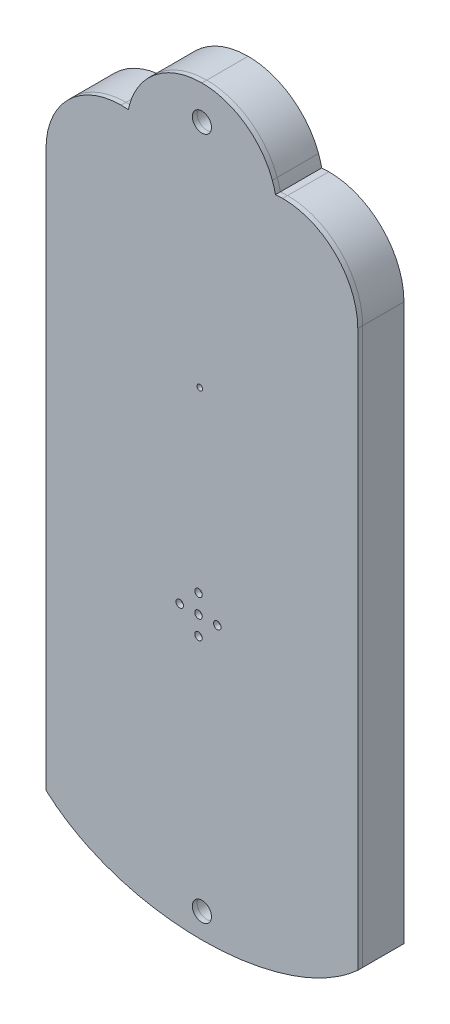
SolidWorks part; units mm, degrees
note: The reader was unsure of these and kept them because the rebuilt part matched: shared geometry of "草图3<3>", "草图3<4>", "草图3<5>", "草图3<6>", "草图3<7>", "草图5<4>", "草图5<5>", "草图5<6>".
ref_plane "前视基准面" through (0, 0, 0) normal (0, 0, 1) x (1, 0, 0)
ref_plane "上视基准面" through (0, 0, 0) normal (0, 1, 0) x (1, 0, 0)
ref_plane "右视基准面" through (0, 0, 0) normal (1, 0, 0) x (0, 0, -1)
other "Configuration Table"
sketch "草图1" plane through (0, 0, 0) normal (0, 0, 1) x (1, 0, 0)
  line L4 (-41.5008, 68.1408) -> (-41.5008, -79.8592)
  line L5 (41.5008, 68.1408) -> (41.5008, -79.8592)
  circle A0 centre (0, 95) radius 2.55
  circle A1 centre (0, -87) radius 2.55
  spline S0 degree 3 poles (41.5008, 68.1408) (41.5008, 79.1863) (32.5473, 88.1398) (21.5018, 88.1398) knots 0 0 0 0 1 1 1 1
  spline S1 degree 3 poles (21.5018, 88.1398) (20.8598, 88.1398) (20.2212, 88.108) (19.5933, 88.048) knots 1 1 1 1 2 2 2 2
  spline S2 degree 3 poles (19.5933, 88.048) (19.3887, 89.0464) (19.1064, 90.0201) (18.7607, 90.962) knots 2 2 2 2 3 3 3 3
  spline S3 degree 3 poles (18.7607, 90.962) (15.9385, 98.582) (8.6043, 104.0148) (0, 104.0148) knots 3 3 3 3 4 4 4 4
  spline S4 degree 3 poles (0, 104.0148) (-8.6043, 104.0148) (-15.9385, 98.582) (-18.7607, 90.962) knots 4 4 4 4 5 5 5 5
  spline S5 degree 3 poles (-18.7607, 90.962) (-19.1065, 90.0201) (-19.3887, 89.0464) (-19.5933, 88.048) knots 5 5 5 5 6 6 6 6
  spline S6 degree 3 poles (-19.5933, 88.048) (-20.2212, 88.108) (-20.8562, 88.1398) (-21.4983, 88.1398) knots 6 6 6 6 7 7 7 7
  spline S7 degree 3 poles (-21.4983, 88.1398) (-32.5473, 88.1398) (-41.5008, 79.1863) (-41.5008, 68.1408) knots 7 7 7 7 8 8 8 8
  spline S9 degree 3 poles (-41.5008, -79.8592) (-38.3893, -82.7026) (-34.5687, -85.2073) (-30.1978, -87.2781) knots 11 11 11 11 12 12 12 12
  spline S10 degree 3 poles (-30.1978, -87.2781) (-21.7805, -91.2681) (-11.3242, -93.6281) (0, -93.6281) knots 12 12 12 12 13 13 13 13
  spline S11 degree 3 poles (0, -93.6281) (11.3242, -93.6281) (21.7805, -91.2681) (30.1978, -87.2781) knots 13 13 13 13 14 14 14 14
  spline S12 degree 3 poles (30.1978, -87.2781) (34.5687, -85.2073) (38.3893, -82.7026) (41.5008, -79.8592) knots 14 14 14 14 15 15 15 15
extrude "凸台-拉伸1" add sketch "草图1" along normal blind 11
ref_plane "基准面1" through (0, 0, 11) normal (0, 0, 1) x (1, 0, 0)
sketch "草图2" plane through (0, 0, 11) normal (0, 0, 1) x (1, 0, 0)
  line L4 (-39, 72.5618) -> (-31.8531, 72.5618)
  line L5 (39, 72.5618) -> (39, -79.4382)
  line L6 (39, -79.4382) -> (33.5901, -79.4382)
  line L7 (-39, -79.4382) -> (-39, 72.5618)
  line L8 (31.8531, 72.5618) -> (39, 72.5618)
  line L9 (-6.9191, -84.6699) -> (-6.9191, -88.937)
  line L10 (-6.9191, -88.937) -> (-32.7537, -79.6163)
  line L11 (5.9471, -84.6699) -> (5.9471, -89.5326)
  line L12 (5.9471, -89.5326) -> (32.543, -79.6269)
  line L13 (-33.7719, -79.4382) -> (-39, -79.4382)
  line L15 (-3.9191, -81.6699) -> (2.9471, -81.6699)
  arc A0 (-32.7537, -79.6163) -> (-33.7719, -79.4382) centre (-33.7719, -82.4382) ccw
  arc A1 (32.543, -79.6269) -> (33.5901, -79.4382) centre (33.5901, -82.4382) cw
  arc A2 (2.9471, -81.6699) -> (5.9471, -84.6699) centre (2.9471, -84.6699) cw
  arc A3 (-3.9191, -81.6699) -> (-6.9191, -84.6699) centre (-3.9191, -84.6699) ccw
  ellipse E0 centre (0, 72.5618) end of major axis (31.8531, 72.5618) minor radius 16.2594 (31.8531, 72.5618) -> (-31.8531, 72.5618) ccw
  point P11 (0, 72.5618)
  point P20 (-33.2472, -79.4382)
  dimension "D1" = 3
extrude "切除-拉伸1" cut sketch "草图2" against normal blind 12
sketch "草图3" plane through (0, 0, 11) normal (0, 0, 1) x (1, 0, 0)
  line L1 (35.4265, -17.4382) -> (39, -17.4382)
  line L2 (39, -79.4382) -> (39, 72.5618) construction
  line L3 (39, -17.4382) -> (39, 72.5618)
  line L4 (39, 72.5618) -> (35.4265, 72.5618)
  line L6 (35.4265, -17.4382) -> (39, -17.4382)
  line L8 (35.4265, -79.4382) -> (39, -79.4382)
  line L9 (39, -17.4382) -> (39, -79.4382)
  line L10 (-39, 72.5618) -> (-35.4265, 72.5618)
  line L11 (-39, 72.5618) -> (-39, 37.5618)
  line L12 (-39, 37.5618) -> (-35.4265, 37.5618)
  line L14 (-39, 37.5618) -> (-35.4265, 37.5618)
  line L15 (-39, 37.5618) -> (-39, 17.5618)
  line L16 (-39, 17.5618) -> (-35.4265, 17.5618)
  line L18 (-39, 17.5618) -> (-35.4265, 17.5618)
  line L19 (-39, 17.5618) -> (-39, -17.4382)
  line L20 (-39, -17.4382) -> (-35.4265, -17.4382)
  line L22 (-39, -17.4382) -> (-35.4265, -17.4382)
  line L23 (-39, -17.4382) -> (-39, -79.4382)
  line L24 (-39, -79.4382) -> (-35.4265, -79.4382)
  line L26 (-39, 45.8739) -> (-35.4265, 45.8739)
  line L27 (20.5419, -14.1047) -> (32.8279, -14.1047)
  line L28 (35.4265, -36.1381) -> (39, -36.1381)
  line L29 (35.4265, -61.3133) -> (39, -61.3133)
  line L30 (-30.8782, -14.1047) -> (-22.35, -14.1047)
  line L32 (-30.7801, -21.1833) -> (-22.7965, -21.1833)
  line L34 (20.9884, -21.1833) -> (32.9261, -21.1833)
  line L35 (-39, 65.5697) -> (-35.4265, 65.5697)
  line L36 (-39, -8.0335) -> (-35.4265, -8.0335)
  line L37 (-39, -26.8837) -> (-35.4265, -26.8837)
  line L38 (-39, -45.9131) -> (-35.4265, -45.9131)
  line L39 (-39, -52.894) -> (-35.4265, -52.894)
  line L40 (-39, -72.037) -> (-35.4265, -72.037)
  line L41 (35.4265, 65.5697) -> (39, 65.5697)
  line L42 (35.4265, 34.3099) -> (39, 34.3099)
  line L43 (35.4265, 21.7239) -> (39, 21.7239)
  line L44 (35.4265, -8.0335) -> (39, -8.0335)
  line L45 (35.4265, 72.5618) -> (35.4265, -79.4382)
  line L46 (-35.4265, 72.5618) -> (-35.4265, -79.4382)
  line L47 (-30.8782, -14.1047) -> (-35.4265, -14.1047)
  line L48 (-30.7801, -21.1833) -> (-35.4265, -21.1833)
  line L49 (32.8279, -14.1047) -> (35.4265, -14.1047)
  line L50 (32.9261, -21.1833) -> (35.4265, -21.1833)
  circle A0 centre (-0.904, -19.0108) radius 20.25
  circle A1 centre (-0.904, -19.0108) radius 22
extrude "凸台-拉伸2" add sketch "草图3" against normal blind 9 separate body contours L4 L45 L41 L3 | L46 L10 L11 L35 | L46 L26 L11 L12 | L42 L45 L43 L3 | L44 L45 L1 L3 | L46 L36 L19 L20
extrude "凸台-拉伸3" add sketch "草图3<3>" against normal blind 2 separate body contours L46 L35 L11 L26 | L41 L45 L42 L3 | L43 L45 L44 L3 | L46 L16 L19 L36 | L46 L12 L15 L16
sketch "草图3<3>" plane through (0, 0, 11) normal (0, 0, 1) x (1, 0, 0) same geometry as "草图3"
extrude "凸台-拉伸4" add sketch "草图3<4>" against normal blind 2
sketch "草图3<4>" plane through (0, 0, 11) normal (0, 0, 1) x (1, 0, 0) same geometry as "草图3"
extrude "凸台-拉伸5" add sketch "草图3<5>" against normal blind 5 contours A1 A0
sketch "草图3<5>" plane through (0, 0, 11) normal (0, 0, 1) x (1, 0, 0) same geometry as "草图3"
extrude "凸台-拉伸6" add sketch "草图3<6>" against normal blind 8.5 separate body
sketch "草图3<6>" plane through (0, 0, 11) normal (0, 0, 1) x (1, 0, 0) same geometry as "草图3"
extrude "凸台-拉伸7" add sketch "草图3<7>" against normal blind 2 separate body contours L46 L37 L23 L38 | L46 L39 L23 L40 | L28 L45 L29 L9
sketch "草图3<7>" plane through (0, 0, 11) normal (0, 0, 1) x (1, 0, 0) same geometry as "草图3"
ref_plane "基准面2" through (0, 0, 11) normal (0, 0, 1) x (1, 0, 0)
sketch "草图5" plane through (0, 0, 11) normal (0, 0, 1) x (1, 0, 0)
  line L0 (26.5783, 72.5618) -> (26.5783, 46.5618) construction
  line L1 (26.5783, 46.5618) -> (35.4265, 46.5618)
  line L3 (35.4265, 46.5618) -> (35.4265, 48.7052)
  line L4 (-41.5008, 68.1408) -> (-41.5008, -79.8592)
  line L5 (41.5008, 68.1408) -> (41.5008, -79.8592)
  line L6 (35.4265, 48.7052) -> (26.5783, 48.7052)
  line L7 (26.5783, 48.7052) -> (26.5783, 46.5618)
  line L8 (26.5783, 46.5618) -> (26.5783, 44.1796)
  line L9 (26.5783, 44.1796) -> (35.4265, 44.1796)
  line L10 (35.4265, 44.1796) -> (35.4265, 46.5618)
  line L11 (-10.106, 14.7667) -> (-10.106, 6.0897)
  line L13 (-10.106, 14.7667) -> (-11.9222, 14.7667)
  line L14 (-11.9222, 14.7667) -> (-11.9222, 4.6475)
  line L15 (-11.9222, 4.6475) -> (-5.538, 4.6475)
  line L16 (-10.106, 6.0897) -> (-5.538, 6.0897)
  line L18 (-5.538, 6.0897) -> (-5.538, 4.6475)
  line L19 (-10.106, 9.0897) -> (-5.538, 9.0897)
  line L20 (-5.538, 9.0897) -> (-5.538, 6.0897)
  line L21 (-10.106, 36.8239) -> (-10.106, 41.8535)
  line L22 (-10.106, 41.8535) -> (-11.9222, 41.8535)
  line L23 (-11.9222, 41.8535) -> (-11.9222, 36.8239)
  line L24 (-11.9222, 36.8239) -> (-10.106, 36.8239)
  line L25 (-10.106, 41.8535) -> (-7.3703, 41.8535)
  line L26 (-7.3703, 41.8535) -> (-7.3703, 36.8239)
  line L27 (-7.3703, 36.8239) -> (-10.106, 36.8239)
  circle A0 centre (0, 95) radius 2.55
  circle A1 centre (0, -87) radius 2.55
  circle A2 centre (-0.5438, 33.4934) radius 0.75
  circle A3 centre (-0.904, -19.0108) radius 1
  circle A5 centre (-0.904, -14.0108) radius 1
  circle A6 centre (4.096, -19.0108) radius 1
  circle A7 centre (-0.904, -24.0108) radius 1
  circle A8 centre (-5.904, -19.0108) radius 1
  spline S0 degree 3 poles (41.5008, 68.1408) (41.5008, 79.1863) (32.5473, 88.1398) (21.5018, 88.1398) knots 0 0 0 0 1 1 1 1
  spline S1 degree 3 poles (21.5018, 88.1398) (20.8598, 88.1398) (20.2212, 88.108) (19.5933, 88.048) knots 1 1 1 1 2 2 2 2
  spline S2 degree 3 poles (19.5933, 88.048) (19.3887, 89.0464) (19.1064, 90.0201) (18.7607, 90.962) knots 2 2 2 2 3 3 3 3
  spline S3 degree 3 poles (18.7607, 90.962) (15.9385, 98.582) (8.6043, 104.0148) (0, 104.0148) knots 3 3 3 3 4 4 4 4
  spline S4 degree 3 poles (0, 104.0148) (-8.6043, 104.0148) (-15.9385, 98.582) (-18.7607, 90.962) knots 4 4 4 4 5 5 5 5
  spline S5 degree 3 poles (-18.7607, 90.962) (-19.1065, 90.0201) (-19.3887, 89.0464) (-19.5933, 88.048) knots 5 5 5 5 6 6 6 6
  spline S6 degree 3 poles (-19.5933, 88.048) (-20.2212, 88.108) (-20.8562, 88.1398) (-21.4983, 88.1398) knots 6 6 6 6 7 7 7 7
  spline S7 degree 3 poles (-21.4983, 88.1398) (-32.5473, 88.1398) (-41.5008, 79.1863) (-41.5008, 68.1408) knots 7 7 7 7 8 8 8 8
  spline S9 degree 3 poles (-41.5008, -79.8592) (-38.3893, -82.7026) (-34.5687, -85.2073) (-30.1978, -87.2781) knots 11 11 11 11 12 12 12 12
  spline S10 degree 3 poles (-30.1978, -87.2781) (-21.7805, -91.2681) (-11.3242, -93.6281) (0, -93.6281) knots 12 12 12 12 13 13 13 13
  spline S11 degree 3 poles (0, -93.6281) (11.3242, -93.6281) (21.7805, -91.2681) (30.1978, -87.2781) knots 13 13 13 13 14 14 14 14
  spline S12 degree 3 poles (30.1978, -87.2781) (34.5687, -85.2073) (38.3893, -82.7026) (41.5008, -79.8592) knots 14 14 14 14 15 15 15 15
  point P49 (-0.904, -19.0108)
  point P52 (-0.904, -19.0108)
extrude "凸台-拉伸8" add sketch "草图5" along normal blind 1.3 separate body
extrude "凸台-拉伸9" add sketch "草图5<4>" against normal blind 9 separate body contours L6 L7 L1 L3 | L18 L16 L11 L13 L14 L15 | L23 L24 L21 L22
sketch "草图5<4>" plane through (0, 0, 11) normal (0, 0, 1) x (1, 0, 0) same geometry as "草图5"
extrude "凸台-拉伸10" add sketch "草图5<5>" against normal blind 7 separate body contours L9 L10 L1 L8 | L20 L19 L11 L16
sketch "草图5<5>" plane through (0, 0, 11) normal (0, 0, 1) x (1, 0, 0) same geometry as "草图5"
extrude "凸台-拉伸11" add sketch "草图5<6>" against normal blind 6 separate body contours L27 L26 L25 L21
sketch "草图5<6>" plane through (0, 0, 11) normal (0, 0, 1) x (1, 0, 0) same geometry as "草图5"
equation "\"、\"=3"
